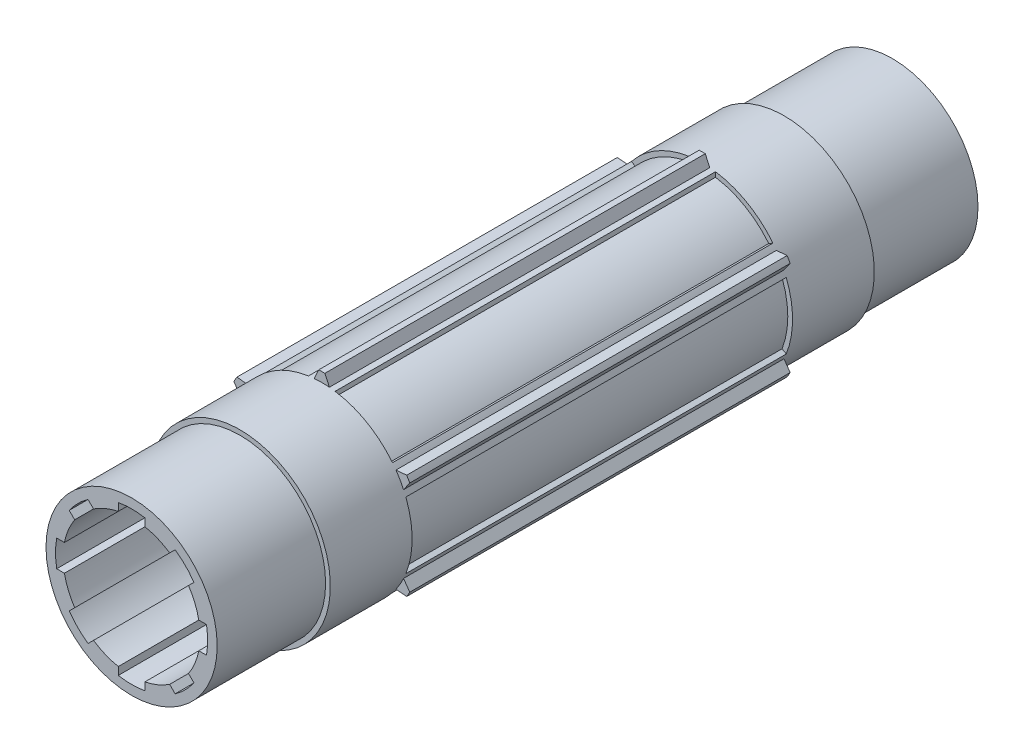
SolidWorks part; units mm, degrees
ref_plane "Front Plane" through (0, 0, 0) normal (0, 0, 1) x (1, 0, 0)
ref_plane "Top Plane" through (0, 0, 0) normal (0, 1, 0) x (1, 0, 0)
ref_plane "Right Plane" through (0, 0, 0) normal (1, 0, 0) x (0, 0, -1)
sketch "Sketch1" plane through (0, 0, 0) normal (0, 0, 1) x (1, 0, 0)
  line L0 (0, 0) -> (0, 33.7674) construction
  line L17 (-3.5, 19.6914) -> (-3.5, 17.6564)
  line L18 (3.5, 19.6914) -> (3.5, 17.6564)
  line L19 (11.449, 16.3988) -> (10.0101, 14.9599)
  line L20 (16.3988, 11.449) -> (14.9599, 10.0101)
  line L21 (19.6914, 3.5) -> (17.6564, 3.5)
  line L22 (19.6914, -3.5) -> (17.6564, -3.5)
  line L23 (16.3988, -11.449) -> (14.9599, -10.0101)
  line L24 (11.449, -16.3988) -> (10.0101, -14.9599)
  line L25 (3.5, -19.6914) -> (3.5, -17.6564)
  line L26 (-3.5, -19.6914) -> (-3.5, -17.6564)
  line L27 (-11.449, -16.3988) -> (-10.0101, -14.9599)
  line L28 (-16.3988, -11.449) -> (-14.9599, -10.0101)
  line L29 (-19.6914, -3.5) -> (-17.6564, -3.5)
  line L30 (-19.6914, 3.5) -> (-17.6564, 3.5)
  line L31 (-16.3988, 11.449) -> (-14.9599, 10.0101)
  line L32 (-11.449, 16.3988) -> (-10.0101, 14.9599)
  circle A17 centre (0, 0) radius 22.5
  arc A18 (-11.449, 16.3988) -> (-16.3988, 11.449) centre (0, 0) ccw
  arc A19 (-3.5, 17.6564) -> (-10.0101, 14.9599) centre (0, 0) ccw
  arc A20 (3.5, 19.6914) -> (-3.5, 19.6914) centre (0, 0) ccw
  arc A21 (10.0101, 14.9599) -> (3.5, 17.6564) centre (0, 0) ccw
  arc A22 (-14.9599, 10.0101) -> (-17.6564, 3.5) centre (0, 0) ccw
  arc A23 (-19.6914, 3.5) -> (-19.6914, -3.5) centre (0, 0) ccw
  arc A24 (-17.6564, -3.5) -> (-14.9599, -10.0101) centre (0, 0) ccw
  arc A25 (-16.3988, -11.449) -> (-11.449, -16.3988) centre (0, 0) ccw
  arc A26 (-10.0101, -14.9599) -> (-3.5, -17.6564) centre (0, 0) ccw
  arc A27 (-3.5, -19.6914) -> (3.5, -19.6914) centre (0, 0) ccw
  arc A28 (3.5, -17.6564) -> (10.0101, -14.9599) centre (0, 0) ccw
  arc A29 (11.449, -16.3988) -> (16.3988, -11.449) centre (0, 0) ccw
  arc A30 (14.9599, -10.0101) -> (17.6564, -3.5) centre (0, 0) ccw
  arc A31 (19.6914, -3.5) -> (19.6914, 3.5) centre (0, 0) ccw
  arc A32 (17.6564, 3.5) -> (14.9599, 10.0101) centre (0, 0) ccw
  arc A33 (16.3988, 11.449) -> (11.449, 16.3988) centre (0, 0) ccw
  point P39 (0, 0)
  dimension "D1" = 3.5
  dimension "D2" = 3.5
extrude "Boss-Extrude1" add sketch "Sketch1" along normal blind 200
sketch "Sketch3" plane through (0, 0, 0) normal (0, 0, 1) x (1, 0, 0)
  line L0 (0, 0) -> (0, 28.873) construction
  line L1 (-2, 23.6656) -> (-0.8006, 26.2378)
  line L2 (2, 23.6656) -> (0.8006, 26.2378)
  line L3 (-3.5, 22.2261) -> (-3.5, 23.4907)
  line L4 (3.5, 22.2261) -> (3.5, 23.4907)
  line L5 (17.4984, 14.1441) -> (18.5935, 14.7764)
  line L6 (19.495, 13.5649) -> (22.3223, 13.8122)
  line L7 (21.495, 10.1008) -> (23.1229, 12.4256)
  line L8 (20.9984, 8.082) -> (22.0935, 8.7143)
  line L9 (20.9984, -8.082) -> (22.0935, -8.7143)
  line L10 (21.495, -10.1008) -> (23.1229, -12.4256)
  line L11 (19.495, -13.5649) -> (22.3223, -13.8122)
  line L12 (17.4984, -14.1441) -> (18.5935, -14.7764)
  line L13 (3.5, -22.2261) -> (3.5, -23.4907)
  line L14 (2, -23.6656) -> (0.8006, -26.2378)
  line L15 (-2, -23.6656) -> (-0.8006, -26.2378)
  line L16 (-3.5, -22.2261) -> (-3.5, -23.4907)
  line L17 (-17.4984, -14.1441) -> (-18.5935, -14.7764)
  line L18 (-19.495, -13.5649) -> (-22.3223, -13.8122)
  line L19 (-21.495, -10.1008) -> (-23.1229, -12.4256)
  line L20 (-20.9984, -8.082) -> (-22.0935, -8.7143)
  line L21 (-20.9984, 8.082) -> (-22.0935, 8.7143)
  line L22 (-21.495, 10.1008) -> (-23.1229, 12.4256)
  line L23 (-19.495, 13.5649) -> (-22.3223, 13.8122)
  line L24 (-17.4984, 14.1441) -> (-18.5935, 14.7764)
  arc A0 (-20.9984, -8.082) -> (-17.4984, -14.1441) centre (0, 0) ccw
  arc A1 (-2, 23.6656) -> (-3.5, 23.4907) centre (0, 0) ccw
  arc A2 (0.8006, 26.2378) -> (-0.8006, 26.2378) centre (0, 0) ccw
  arc A3 (2, 23.6656) -> (3.5, 23.4907) centre (0, 0) cw
  arc A4 (19.495, 13.5649) -> (18.5935, 14.7764) centre (0, 0) ccw
  arc A5 (23.1229, 12.4256) -> (22.3223, 13.8122) centre (0, 0) ccw
  arc A6 (21.495, 10.1008) -> (22.0935, 8.7143) centre (0, 0) cw
  arc A7 (21.495, -10.1008) -> (22.0935, -8.7143) centre (0, 0) ccw
  arc A8 (22.3223, -13.8122) -> (23.1229, -12.4256) centre (0, 0) ccw
  arc A9 (19.495, -13.5649) -> (18.5935, -14.7764) centre (0, 0) cw
  arc A10 (2, -23.6656) -> (3.5, -23.4907) centre (0, 0) ccw
  arc A11 (-0.8006, -26.2378) -> (0.8006, -26.2378) centre (0, 0) ccw
  arc A12 (-2, -23.6656) -> (-3.5, -23.4907) centre (0, 0) cw
  arc A13 (-19.495, -13.5649) -> (-18.5935, -14.7764) centre (0, 0) ccw
  arc A14 (-23.1229, -12.4256) -> (-22.3223, -13.8122) centre (0, 0) ccw
  arc A15 (-21.495, -10.1008) -> (-22.0935, -8.7143) centre (0, 0) cw
  arc A16 (-21.495, 10.1008) -> (-22.0935, 8.7143) centre (0, 0) ccw
  arc A17 (-22.3223, 13.8122) -> (-23.1229, 12.4256) centre (0, 0) ccw
  arc A18 (-19.495, 13.5649) -> (-18.5935, 14.7764) centre (0, 0) cw
  arc A19 (-17.4984, 14.1441) -> (-20.9984, 8.082) centre (0, 0) ccw
  arc A20 (3.5, 22.2261) -> (-3.5, 22.2261) centre (0, 0) ccw
  arc A21 (20.9984, 8.082) -> (17.4984, 14.1441) centre (0, 0) ccw
  arc A22 (17.4984, -14.1441) -> (20.9984, -8.082) centre (0, 0) ccw
  arc A23 (-3.5, -22.2261) -> (3.5, -22.2261) centre (0, 0) ccw
  point P55 (0, 0)
  dimension "D1" = 45
extrude "Boss-Extrude2" add sketch "Sketch3" along normal blind 100 from offset 50
sketch "Sketch4" plane through (0, 0, 200) normal (0, 0, 1) x (1, 0, 0)
  circle A0 centre (0, 0) radius 23.75
  circle A1 centre (0, 0) radius 22.5
  dimension "D1" = 45
  dimension "D2" = 47.5
extrude "Boss-Extrude3" add sketch "Sketch4" along normal blind 21.5 from surface starting at face at (20.7359, 11.9719, 150)
extrude "Boss-Extrude4" add sketch "Sketch4<2>" against normal blind 21.5 from surface starting at face at (0, 23.9438, 50)
sketch "Sketch4<2>" plane through (0, 0, 200) normal (0, 0, 1) x (1, 0, 0) same geometry as "Sketch4"
